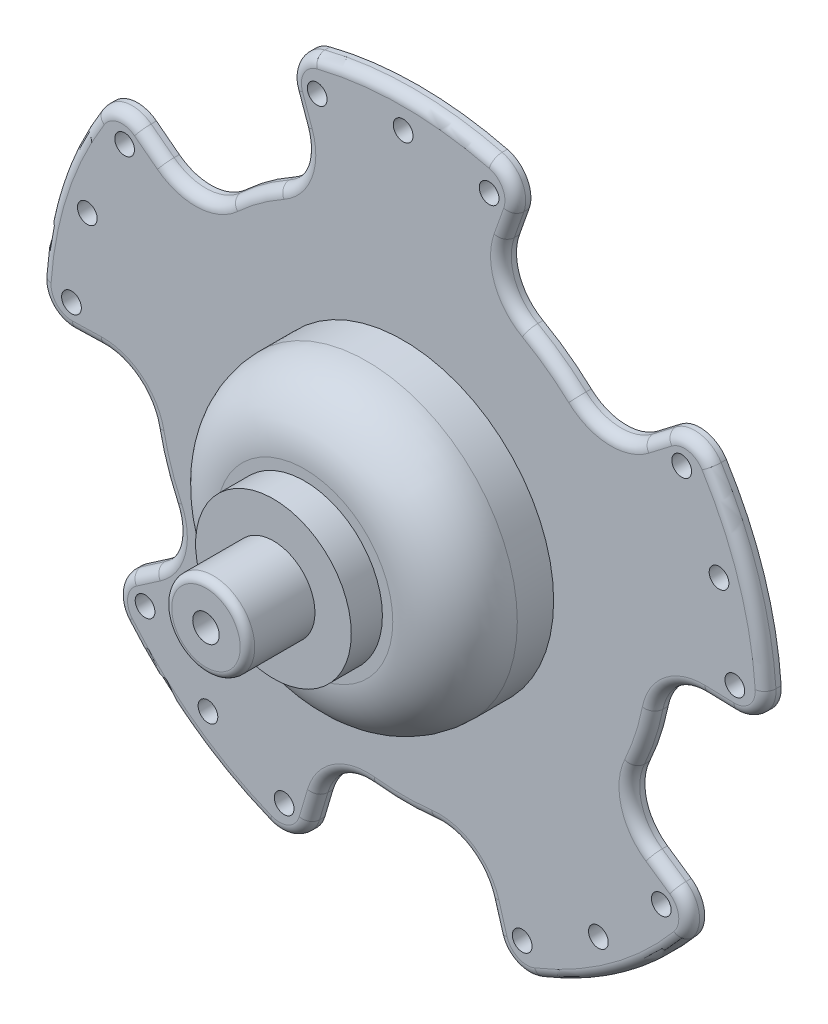
SolidWorks part; units mm, degrees
ref_plane "Front Plane" through (0, 0, 0) normal (0, 0, 1) x (1, 0, 0)
ref_plane "Top Plane" through (0, 0, 0) normal (0, 1, 0) x (1, 0, 0)
ref_plane "Right Plane" through (0, 0, 0) normal (1, 0, 0) x (0, 0, -1)
ref_axis "X-Axis" through (-88.99, 0, 0) along (1, 0, 0)
ref_axis "Y-Axis" through (0, 55, 0) along (0, -1, 0)
ref_axis "Z-Axis" through (0, 0, -88.99) along (0, 0, 1)
sketch "Sketch1" plane through (0, 0, 0) normal (0, 0, 1) x (1, 0, 0)
  circle A0 centre (0, 0) radius 35
  circle A1 centre (0, 0) radius 12.5
  dimension "D1" = 70
  dimension "D2" = 25
extrude "Boss-Extrude1" add sketch "Sketch1" along normal blind 1.5
sketch "Sketch5" plane through (0, 0, 1.5) normal (0, 0, 1) x (1, 0, 0)
  line L0 (0, 0) -> (0, 32) construction
  circle A0 centre (0, 32) radius 0.95
  dimension "D1" = 1.9
  dimension "D2" = 32
extrude "Cut-Extrude1" cut sketch "Sketch5" against normal through all
pattern_circular "CirPattern4" count 2 over 15 about axis through (0, 0, -88.99) along (0, 0, 1) of "Cut-Extrude1" reverse direction yes
pattern_circular "CirPattern3" count 2 over 15 about axis through (0, 0, -88.99) along (0, 0, 1) of "Cut-Extrude1"
sketch "Sketch2" plane through (0, 0, 1.5) normal (0, 0, 1) x (1, 0, 0)
  circle A3 centre (0, 0) radius 12.5
  circle A4 centre (0, 0) radius 12.5
  dimension "D1" = 0
extrude "Extrude-Thin1" add sketch "Sketch2" along normal blind 9.5 thin thin type one direction wall 2
pattern_circular "CirPattern1" count 5 over 360 about axis through (0, 0, -88.99) along (0, 0, 1) of "Cut-Extrude1", "CirPattern4", "CirPattern3"
sketch "Sketch3" plane through (0, 0, 0) normal (0, 0, -1) x (-1, 0, 0)
  circle A1 centre (0, 0) radius 1.275
  circle A2 centre (0, 0) radius 12.5
  circle A3 centre (0, 0) radius 12.5
  dimension "D2" = 2.55
  dimension "D1" = 0
extrude "Boss-Extrude2" add sketch "Sketch3" against normal blind 3 from offset 8 offset against normal yes
fillet "Fillet1" radius 3 1 edges at (-12.5, 0, 8)
fillet "Fillet2" radius 6 1 edges at (14.5, 0, 11)
sketch "Sketch6" plane through (0, 0, 11) normal (0, 0, 1) x (1, 0, 0)
  circle A1 centre (0, 0) radius 4
  circle A2 centre (0, 0) radius 1.275
  circle A3 centre (0, 0) radius 1.275
  dimension "D2" = 8
  dimension "D1" = 0
extrude "Boss-Extrude3" add sketch "Sketch6" along normal blind 9.5
sketch "Sketch7" plane through (0, 0, 11) normal (0, 0, 1) x (1, 0, 0)
  circle A1 centre (0, 0) radius 7.5
  circle A2 centre (0, 0) radius 4
  circle A3 centre (0, 0) radius 4
  dimension "D2" = 15
  dimension "D1" = 0
extrude "Boss-Extrude4" add sketch "Sketch7" along normal blind 3
sketch "Sketch8" plane through (0, 0, 1.5) normal (0, 0, 1) x (1, 0, 0)
  line L0 (0, 32) -> (0, 0) construction
  line L1 (0, 0) -> (30.4338, 9.8885) construction
  line L2 (0, 0) -> (20.5725, 28.3156) construction
  line L3 (0, 0) -> (11.6832, 32.9925) construction
  line L4 (0, 0) -> (27.7674, 21.3067) construction
  line L5 (11.6832, 32.9925) -> (8.1783, 23.0947)
  line L6 (19.4372, 14.9147) -> (27.7674, 21.3067)
  circle A2 centre (0, 0) radius 24.5
  arc A3 (19.4372, 14.9147) -> (8.1783, 23.0947) centre (0, 0) ccw
  arc A4 (0, 24.5) -> (23.3009, 7.5709) centre (0, 0) ccw construction
  circle A5 centre (0, 0) radius 35
  arc A6 (27.7674, 21.3067) -> (11.6832, 32.9925) centre (0, 0) ccw
  dimension "D3" = 36
  dimension "D4" = 16.5
  dimension "D5" = 16.5
  dimension "D1" = 10
  dimension "D2" = 0
extrude "Cut-Extrude2" cut sketch "Sketch8" against normal through all
fillet "Fillet3" radius 3 2 edges at (27.7674, 21.3067, 0.75) (11.6832, 32.9925, 0.75)
fillet "Fillet4" radius 5 2 edges at (19.4372, 14.9147, 0.75) (8.1783, 23.0947, 0.75)
pattern_circular "CirPattern2" count 5 over 360 about axis through (0, 0, -88.99) along (0, 0, 1) of "Cut-Extrude2", "Fillet4", "Fillet3"
fillet "Fillet5" radius 1 40 edges at (-27.6325, 19.9672, 1.5) (-24.1704, 18.5466, 1.5) (-19.7929, 16.6706, 1.5) (-14.4007, 19.8209, 1.5) (-9.7384, 23.9756, 1.5) (-10.1698, 28.7186, 1.5) (-10.451, 32.4503, 1.5) (0, 35, 1.5) (10.451, 32.4503, 1.5) (10.1698, 28.7186, 1.5) (9.7384, 23.9756, 1.5) (14.4007, 19.8209, 1.5) (19.7929, 16.6706, 1.5) (24.1704, 18.5466, 1.5) (27.6325, 19.9672, 1.5) (33.287, 10.8156, 1.5) (34.0916, 0.0882, 1.5) (30.4557, -0.7975, 1.5) (25.8115, -1.8529, 1.5) (23.3009, -7.5709, 1.5) (21.971, -13.6726, 1.5) (25.1079, -17.2562, 1.5) (27.5288, -20.1099, 1.5) (20.5725, -28.3156, 1.5) (10.6187, -32.3958, 1.5) (8.6528, -29.2115, 1.5) (6.214, -25.1208, 1.5) (0, -24.5, 1.5) (-6.214, -25.1208, 1.5) (-8.6528, -29.2115, 1.5) (-10.6187, -32.3958, 1.5) (-20.5725, -28.3156, 1.5) (-27.5288, -20.1099, 1.5) (-25.1079, -17.2562, 1.5) (-21.971, -13.6726, 1.5) (-23.3009, -7.5709, 1.5) (-25.8115, -1.8529, 1.5) (-30.4557, -0.7975, 1.5) (-34.0916, 0.0882, 1.5) (-33.287, 10.8156, 1.5)
fillet "Fillet6" radius 0.7 1 edges at (4, 0, 20.5)
equation "\"D5@Sketch8\"=\"D4@Sketch8\""
